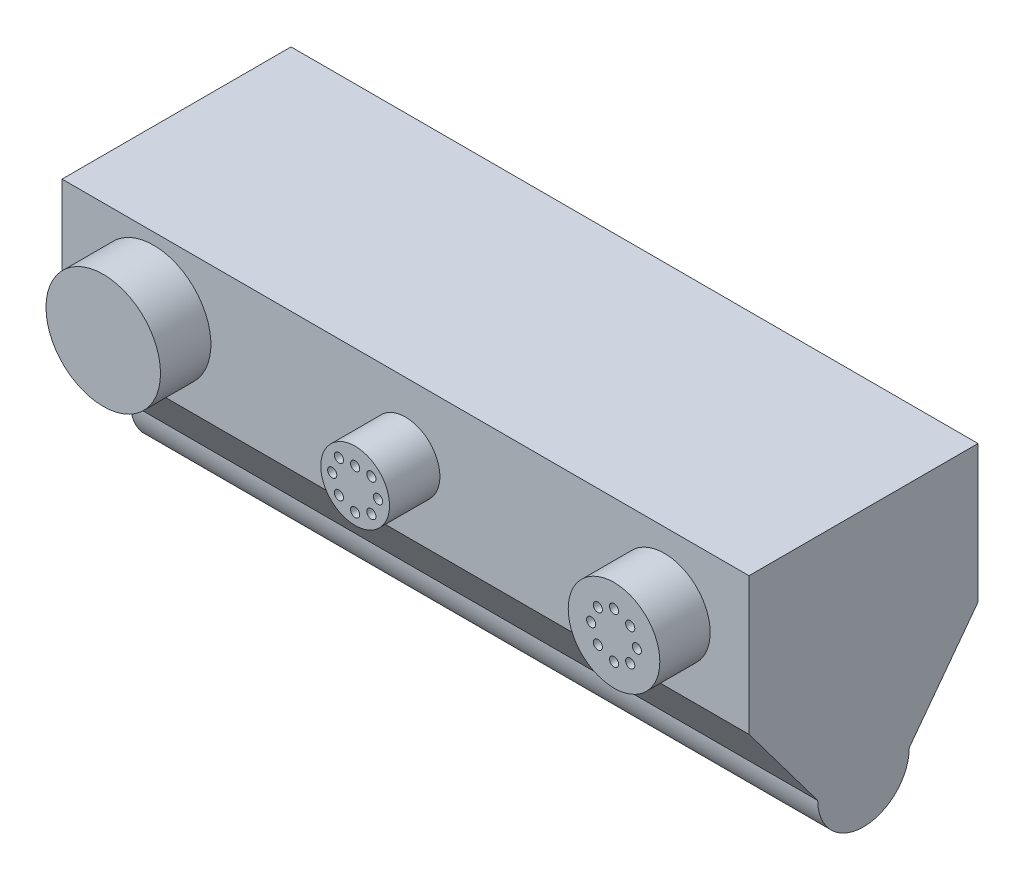
SolidWorks part; units mm, degrees
material "Titan"
ref_plane "Ebene vorne" through (0, 0, 0) normal (0, 0, 1) x (1, 0, 0)
ref_plane "Ebene oben" through (0, 0, 0) normal (0, 1, 0) x (1, 0, 0)
ref_plane "Ebene rechts" through (0, 0, 0) normal (1, 0, 0) x (0, 0, -1)
sketch "Skizze1" plane through (0, 0, 0) normal (0, 1, 0) x (1, 0, 0)
  line L1 (-75, 25) -> (75, 25)
  line L2 (-75, 25) -> (-75, -25)
  line L3 (-75, -25) -> (75, -25)
  line L4 (75, 25) -> (75, -25)
  line L5 (-75, 25) -> (75, -25) construction
  line L6 (-75, -25) -> (75, 25) construction
  point P0 (0, 0)
  dimension "D1" = 50
  dimension "D2" = 150
extrude "Aufsatz-Linear austragen1" add sketch "Skizze1" along normal blind 50
sketch "Skizze2" plane through (75, 0, 0) normal (1, 0, 0) x (0, 0, -1)
  circle A0 centre (0, 0) radius 10
  dimension "D1" = 20
extrude "Aufsatz-Linear austragen2" add sketch "Skizze2" against normal up to surface (150 mm away) up to face at (-75, 25, 0)
sketch "Skizze3" plane through (75, 0, 0) normal (1, 0, 0) x (0, 0, -1)
  line L0 (-10, 0) -> (-25, 20)
  line L1 (-25, 50) -> (-25, 0) construction
  line L2 (-25, 20) -> (-25, 0)
  line L3 (-25, 0) -> (-10, 0)
  line L4 (0, 33) -> (0, -33) construction
  line L5 (25, 20) -> (25, 0)
  line L6 (10, 0) -> (25, 20)
  line L7 (25, 0) -> (10, 0)
  dimension "D1" = 20
extrude "Schnitt-Linear austragen1" cut sketch "Skizze3" against normal blind 182
sketch "Skizze4" plane through (0, 0, 25) normal (0, 0, 1) x (1, 0, 0)
  line L0 (-75, 35) -> (75, 35) construction
  line L1 (-75, 50) -> (-75, 20) construction
  line L2 (75, 50) -> (75, 20) construction
  line L3 (56.5262, 35) -> (56.5262, 45) construction
  line L5 (0, 35) -> (0, 42.5) construction
  circle A0 centre (-55, 35) radius 12.5
  circle A1 centre (56.5262, 35) radius 10
  circle A2 centre (56.5262, 40) radius 1
  circle A3 centre (60.0617, 38.5355) radius 1
  circle A4 centre (61.5262, 35) radius 1
  circle A5 centre (60.0617, 31.4645) radius 1
  circle A6 centre (56.5262, 30) radius 1
  circle A7 centre (52.9907, 31.4645) radius 1
  circle A8 centre (51.5262, 35) radius 1
  circle A9 centre (52.9907, 38.5355) radius 1
  circle A19 centre (0, 35) radius 7.5
  circle A20 centre (0, 38.75) radius 1
  circle A21 centre (3.5355, 38.5355) radius 1
  circle A22 centre (5, 35) radius 1
  circle A23 centre (3.5355, 31.4645) radius 1
  circle A24 centre (0, 30) radius 1
  circle A25 centre (-3.5355, 31.4645) radius 1
  circle A26 centre (-5, 35) radius 1
  circle A27 centre (-3.5355, 38.5355) radius 1
  point P30 (56.5262, 35)
  point P70 (0, 35)
  dimension "D1" = 25
  dimension "D3" = 20
  dimension "D4" = 2
  dimension "D6" = 15
  dimension "D2" = 20
  dimension "D5" = 8
extrude "Aufsatz-Linear austragen3" add sketch "Skizze4" along normal blind 11
